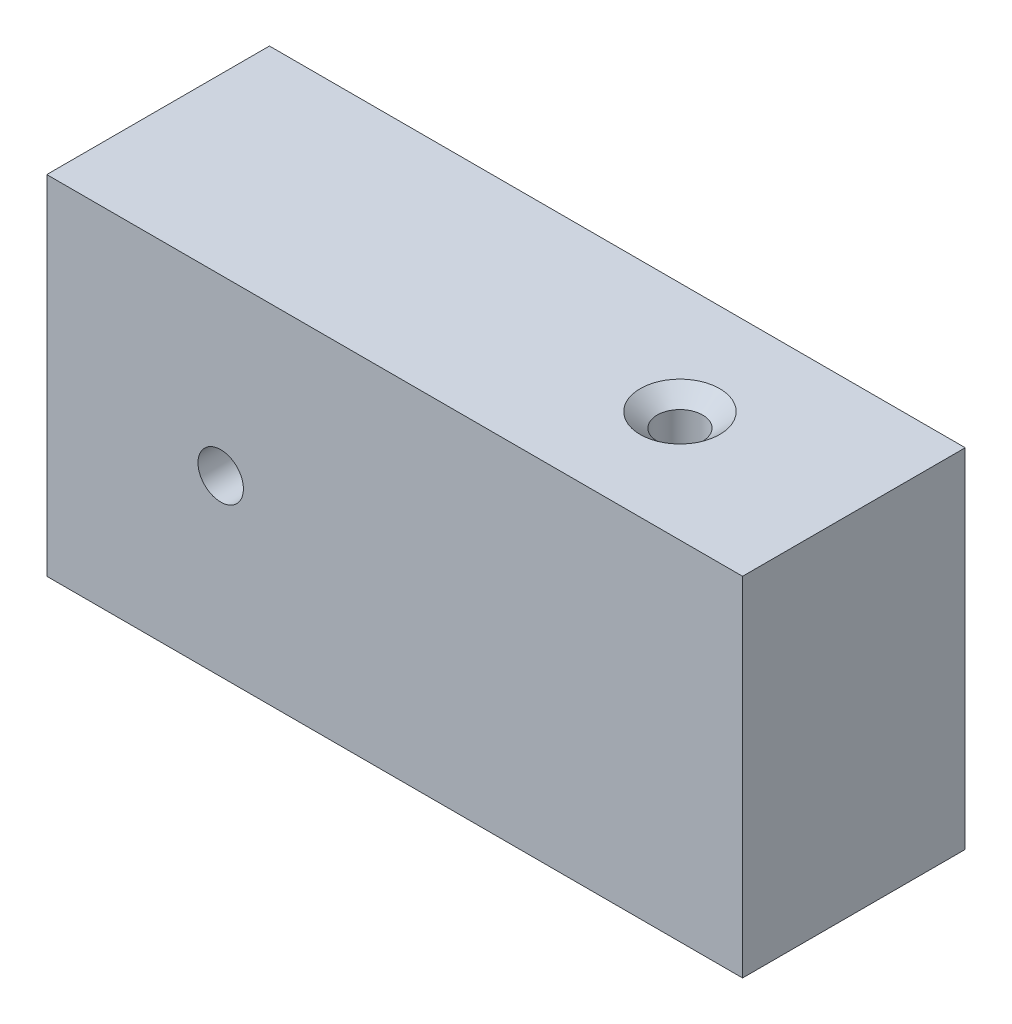
SolidWorks part; units mm, degrees
ref_plane "Front Plane" through (0, 0, 0) normal (0, 0, 1) x (1, 0, 0)
ref_plane "Top Plane" through (0, 0, 0) normal (0, 1, 0) x (1, 0, 0)
ref_plane "Right Plane" through (0, 0, 0) normal (1, 0, 0) x (0, 0, -1)
sketch "Sketch1" plane through (0, 0, 0) normal (0, 0, 1) x (1, 0, 0)
  line L1 (-25, 12.5) -> (25, 12.5)
  line L2 (-25, 12.5) -> (-25, -12.5)
  line L3 (-25, -12.5) -> (25, -12.5)
  line L4 (25, 12.5) -> (25, -12.5)
  point P4 (0, 12.5)
  point P5 (25, 0)
  dimension "D1" = 25
  dimension "D2" = 50
extrude "Boss-Extrude1" add sketch "Sketch1" against normal blind 16 contours L2 L3 L4 L1
hole_wizard "CSK for #4 Flat Head Machine Screw (100)1" positions "3DSketch1" profile "Sketch2" countersink size "#4" standard "ANSI Inch" end condition up to next
sketch3d "3DSketch1"
  line L2 (-25, 12.5, -16) -> (25, 12.5, -16) construction
  line L3 (-25, 12.5, -16) -> (-25, -12.5, -16) construction
  point P4 (-12.5, 0, -16)
  point P17 (0, 0, 0)
  dimension "D1" = 12.5
  dimension "D2" = 12.5
sketch "Sketch2" plane through (-12.5, 0, -16) normal (1, 0, 0) x (0, 1, 0)
  line L0 (0, 0) -> (0, 16)
  line L1 (0, 16) -> (1.6319, 16)
  line L2 (1.6319, 16) -> (1.6319, 1.0284)
  line L3 (1.6319, 1.0284) -> (2.8575, 0)
  line L5 (2.8575, 0) -> (0, 0)
  line L6 (-1.6319, 1.0284) -> (-2.8575, 0) construction
  line L11 (0, -6.35) -> (0, 107.95) construction
  dimension "Thru Hole Dia." = 3.2639
  dimension "Thru Hole Depth" = 16
  dimension "Near C'Sink Dia." = 5.715
  dimension "Near C'Sink Angle" = 100
hole_wizard "CSK for #4 Flat Head Machine Screw (100)2" positions "Sketch3" profile "Sketch4" countersink size "#4" standard "ANSI Inch" end condition up to next
sketch "Sketch3" plane through (0, 12.5, 0) normal (0, 1, 0) x (1, 0, 0)
  line L1 (25, 16) -> (25, 0) construction
  line L2 (-25, 16) -> (25, 16) construction
  point P0 (12.5, 8)
  point P12 (0, 0)
  dimension "D2" = 12.5
  dimension "D3" = 8
sketch "Sketch4" plane through (12.5, 12.5, -8) normal (1, 0, 0) x (0, 0, 1)
  line L0 (0, 0) -> (0, 25)
  line L1 (0, 25) -> (1.6319, 25)
  line L2 (1.6319, 25) -> (1.6319, 1.0284)
  line L3 (1.6319, 1.0284) -> (2.8575, 0)
  line L5 (2.8575, 0) -> (0, 0)
  line L6 (-1.6319, 1.0284) -> (-2.8575, 0) construction
  line L11 (0, -6.35) -> (0, 107.95) construction
  dimension "Thru Hole Dia." = 3.2639
  dimension "Thru Hole Depth" = 25
  dimension "Near C'Sink Dia." = 5.715
  dimension "Near C'Sink Angle" = 100
